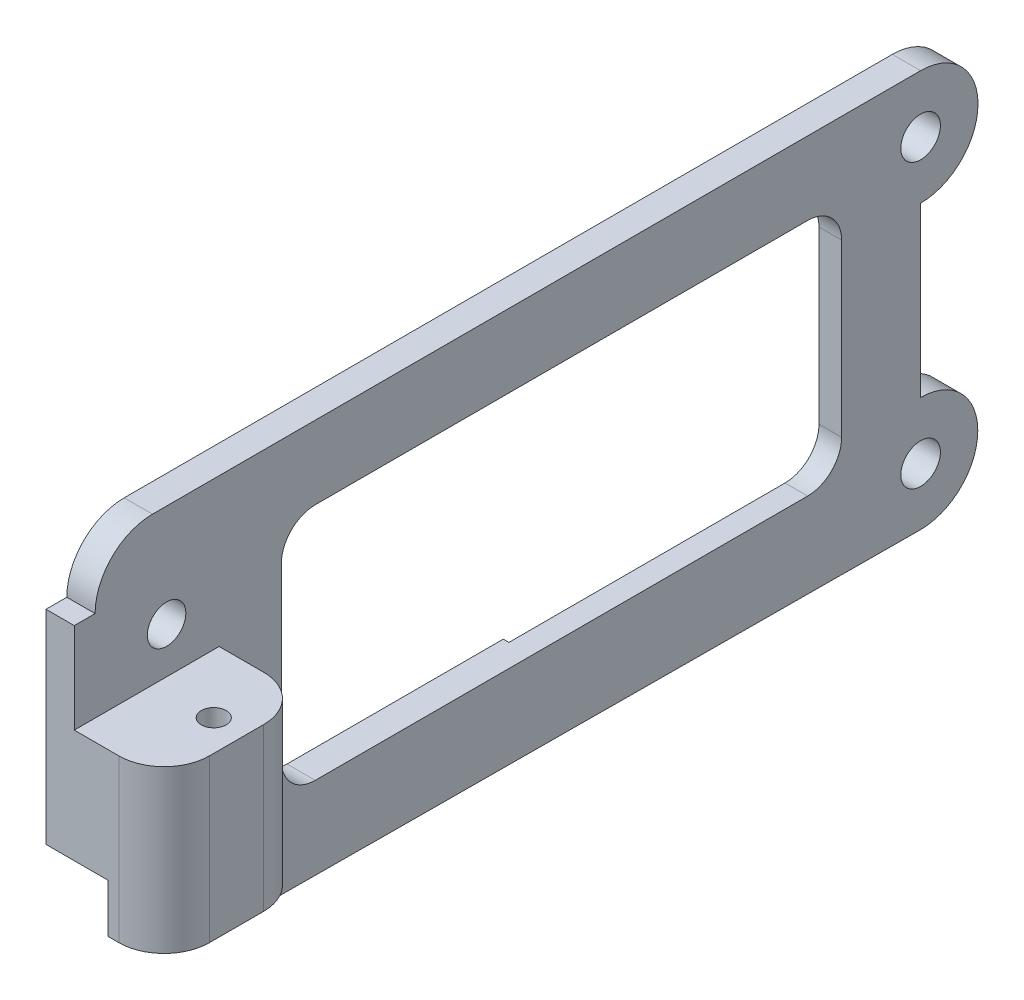
SolidWorks part; units mm, degrees
ref_plane "Front Plane" through (0, 0, 0) normal (0, 0, 1) x (1, 0, 0)
ref_plane "Top Plane" through (0, 0, 0) normal (0, 1, 0) x (1, 0, 0)
ref_plane "Right Plane" through (0, 0, 0) normal (1, 0, 0) x (0, 0, -1)
sketch "Sketch1" plane through (0, 0, 0) normal (1, 0, 0) x (0, 0, -1)
  line L1 (-15, -10) -> (15, -10)
  line L2 (-15, -10) -> (-15, 10)
  line L3 (-15, 10) -> (15, 10)
  line L4 (15, -10) -> (15, 10)
  line L5 (-15, -10) -> (15, 10) construction
  line L6 (-15, 10) -> (15, -10) construction
  point P0 (0, 0)
  dimension "D1" = 30
  dimension "D2" = 20
extrude "Boss-Extrude1" add sketch "Sketch1" along normal blind 2
sketch "Sketch2" plane through (2, 0, 0) normal (1, 0, 0) x (0, 0, -1)
  line L0 (-38.7897, 8.0159) -> (-38.7897, 6.4759) construction
  line L7 (-39.2897, 7.2459) -> (-38.7897, 7.2459)
  line L10 (-48.5016, 18.42) -> (19.3863, 18.42)
  line L11 (19.3863, -6.597) -> (19.3863, 8.2719)
  line L12 (19.3863, -16.7112) -> (-41.3297, -16.3841)
  line L13 (-41.3297, -16.3841) -> (-41.7534, -4.6561)
  line L15 (-41.7534, -4.6561) -> (-55.4147, -4.6561)
  line L16 (-55.4147, -4.6561) -> (-55.4147, 13.3459)
  line L17 (-55.4147, 13.3459) -> (-53.5756, 13.3459)
  circle A0 centre (19.3863, 13.3459) radius 5.074
  circle A1 centre (19.3863, -11.6541) radius 5.0571
  arc A2 (-48.5016, 18.42) -> (-53.5756, 13.3459) centre (-48.5016, 13.3459) ccw
  circle A3 centre (19.3863, 13.3459) radius 1.75
  circle A7 centre (19.3863, -11.6541) radius 1.75
  circle A8 centre (-5.7683, -3.8097) radius 1.5
  line M5 (15, -10) -> (15, 10)
  line M8 (-15, -10) -> (15, -10)
  dimension "D2" = 3.5
  dimension "D3" = 3.5
  dimension "D4" = 3
extrude "Boss-Extrude2" add sketch "Sketch2" against normal blind 2.5 contours A2 L17 L16 L15 L13 L12 A1 L11 A0 L10 | A1 L12 A7 M5 M8 | A0 A3 | A2 region at (2, 17.5509, 52.7065) region at (2, 2.2137, 22.5641) region at (2, 16.8324, -22.8727)
sketch "Sketch5" plane through (2, 0, 0) normal (1, 0, 0) x (0, 0, -1)
  line L0 (-42.6137, -22.1541) -> (-42.6137, 23.8459) construction
  line L1 (-55.4147, -4.6561) -> (-42.6137, -4.6561)
  line L2 (-55.4147, -4.6561) -> (-55.4147, 5.3439)
  line L3 (-55.4147, 5.3439) -> (-42.6137, 5.3439)
  line L4 (-42.6137, -4.6561) -> (-42.6137, 5.3439)
  dimension "D1" = 10
extrude "Boss-Extrude3" add sketch "Sketch5" along normal blind 7.9429
sketch "Sketch6" plane through (4.063, -4.6561, -0.6412) normal (0, -1, 0) x (1, 0, 0)
  circle A0 centre (3.15, 48.9414) radius 1.1
extrude "Cut-Extrude3" cut sketch "Sketch6" against normal blind 10.3509
sketch "Sketch7" plane through (2, 0, 0) normal (1, 0, 0) x (0, 0, -1)
  line L1 (-34.1126, 11.9437) -> (9.4045, 11.9437)
  line L2 (-37.1126, 8.9437) -> (-37.1126, -6.1486)
  line L3 (-34.1126, -9.1486) -> (9.4045, -9.1486)
  line L4 (12.4045, 8.9437) -> (12.4045, -6.1486)
  arc A0 (9.4045, 11.9437) -> (12.4045, 8.9437) centre (9.4045, 8.9437) cw
  arc A1 (9.4045, -9.1486) -> (12.4045, -6.1486) centre (9.4045, -6.1486) ccw
  arc A2 (-37.1126, -6.1486) -> (-34.1126, -9.1486) centre (-34.1126, -6.1486) ccw
  arc A3 (-34.1126, 11.9437) -> (-37.1126, 8.9437) centre (-34.1126, 8.9437) ccw
  dimension "D1" = 3
extrude "Cut-Extrude4" cut sketch "Sketch7" against normal blind 10
sketch "Sketch8" plane through (0, -4.6561, 0) normal (0, -1, 0) x (1, 0, 0)
  line L0 (9.9429, 42.6137) -> (2, 42.6137) construction
  line L1 (9.9429, 55.4147) -> (4.9851, 55.4147)
  line L2 (9.9429, 55.4147) -> (9.9429, 42.6137)
  line L3 (9.9429, 42.6137) -> (4.9851, 42.6137)
  line L4 (4.9851, 55.4147) -> (4.9851, 42.6137)
  circle A0 centre (7.213, 48.3003) radius 1.1
extrude "Boss-Extrude4" add sketch "Sketch8" along normal blind 4.3
fillet "Fillet2" radius 4 2 edges at (9.9429, -1.8061, 42.6137) (9.9429, -1.8061, 55.4147)
sketch "Sketch9" plane through (2, 0, 0) normal (1, 0, 0) x (0, 0, -1)
  circle A0 centre (-47.2557, 9.378) radius 1.7
  dimension "D1" = 3.4
extrude "Cut-Extrude5" cut sketch "Sketch9" against normal blind 5
